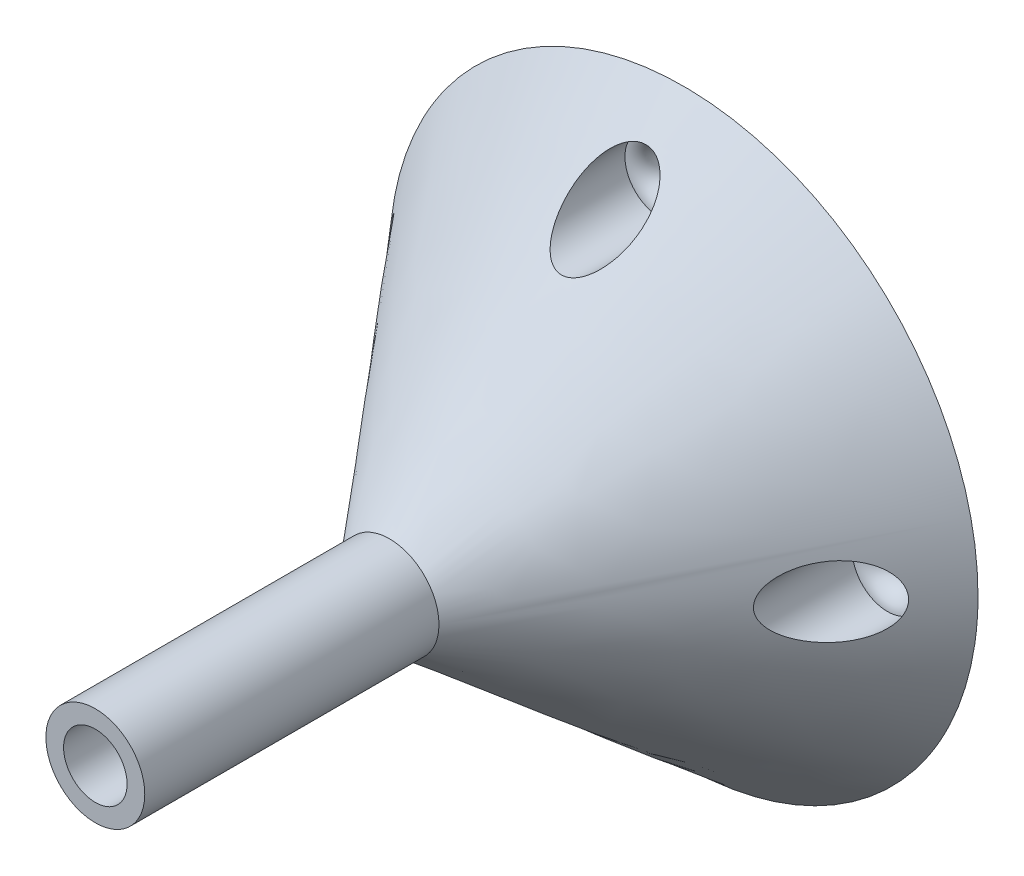
SolidWorks part; units mm, degrees
ref_plane "Piano frontale" through (0, 0, 0) normal (0, 0, 1) x (1, 0, 0)
ref_plane "Piano superiore" through (0, 0, 0) normal (0, 1, 0) x (1, 0, 0)
ref_plane "Piano destro" through (0, 0, 0) normal (1, 0, 0) x (0, 0, -1)
sketch "Schizzo1" plane through (0, 0, 0) normal (0, 0, 1) x (1, 0, 0)
  circle A0 centre (0, 0) radius 25
  dimension "D1" = 50
ref_plane "Piano1" through (0, 0, 25) normal (0, 0, 1) x (1, 0, 0)
sketch "Schizzo2" plane through (0, 0, 25) normal (0, 0, 1) x (1, 0, 0)
  circle A0 centre (0, 0) radius 4.2
  dimension "D1" = 8.4
loft "Loft1" add profiles "Schizzo1", "Schizzo2" connector at (-24.2224, 6.1868, 0) connector at (-3.7422, 1.9068, 25)
sketch "Schizzo3" plane through (0, 0, 25) normal (0, 0, 1) x (1, 0, 0)
  circle A0 centre (0, 0) radius 4.2
  dimension "D1" = 8.4
extrude "Estrusione-Estrusione1" add sketch "Schizzo3" along normal blind 25
sketch "Schizzo4" plane through (0, 0, 25) normal (0, 0, 1) x (1, 0, 0)
  line L0 (0, 0) -> (37.31, 0) construction
  line L1 (0, 0) -> (0, -28.2252) construction
  circle A0 centre (0, 19.3147) radius 1.6
  circle A1 centre (19.3147, 0) radius 1.6
  circle A2 centre (0, -19.3147) radius 1.6
  circle A3 centre (-19.3147, 0) radius 1.6
  point P15 (0, 0)
  dimension "D1" = 3.2
  dimension "D2" = 4
extrude "Taglio-Estrusione1" cut sketch "Schizzo4" against normal blind 25
sketch "Schizzo5" plane through (0, 0, 25) normal (0, 0, 1) x (1, 0, 0)
  circle A0 centre (0, 19.3147) radius 3
  circle A1 centre (19.3147, 0) radius 3
  circle A2 centre (0, -19.3147) radius 3
  circle A3 centre (-19.3147, 0) radius 3
  point P12 (0, 0)
  dimension "D1" = 6
  dimension "D2" = 4
extrude "Taglio-Estrusione2" cut sketch "Schizzo5" against normal blind 23
fillet "Raccordo1" radius 1.5 1 edges at (-17.7147, 0, 2)
fillet "Raccordo2" radius 1.5 1 edges at (1.6, 19.3147, 2)
fillet "Raccordo3" radius 1.5 1 edges at (20.9147, 0, 2)
fillet "Raccordo4" radius 1.5 1 edges at (1.6, -19.3147, 2)
sketch "Schizzo6" plane through (0, 0, 50) normal (0, 0, 1) x (1, 0, 0)
  circle A0 centre (0, 0) radius 2.7
  dimension "D1" = 5.4
extrude "Taglio-Estrusione3" cut sketch "Schizzo6" against normal blind 21
sketch "Schizzo7" plane through (0, 0, 0) normal (0, 1, 0) x (1, 0, 0)
  circle A0 centre (0, -44.7384) radius 1.6
  dimension "D1" = 3.2
extrude "Taglio-Estrusione4" cut sketch "Schizzo7" against normal blind 21
